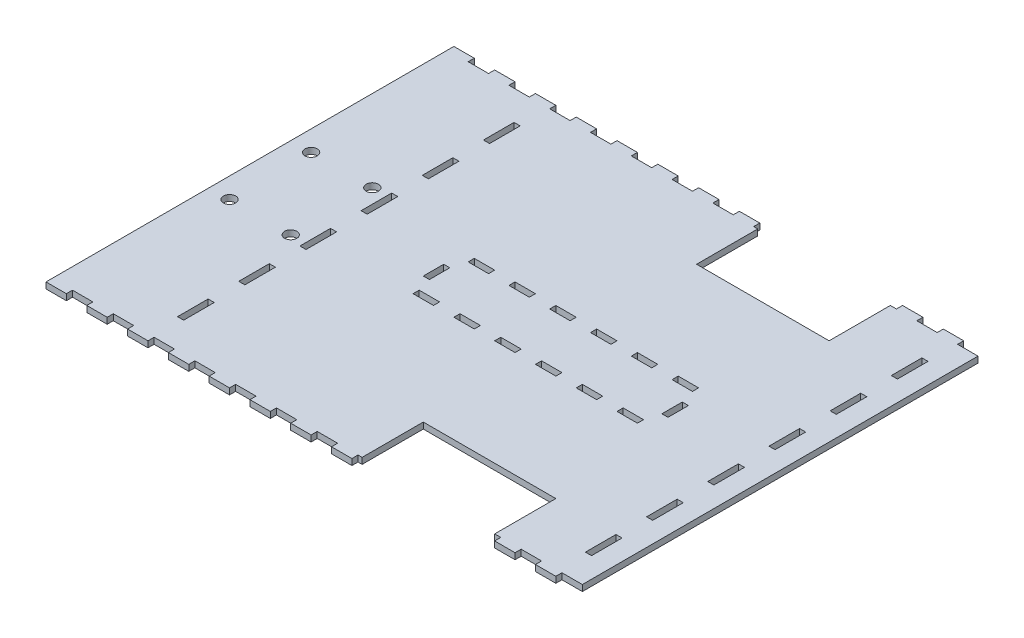
SolidWorks part; units mm, degrees
ref_plane "Front Plane" through (0, 0, 0) normal (0, 0, 1) x (1, 0, 0)
ref_plane "Top Plane" through (0, 0, 0) normal (0, 1, 0) x (1, 0, 0)
ref_plane "Right Plane" through (0, 0, 0) normal (1, 0, 0) x (0, 0, -1)
sketch "Sketch3" plane through (0, 0, 0) normal (0, 1, 0) x (1, 0, 0)
  line L0 (0, 0) -> (-300, 0) construction
  line L1 (-300, -97) -> (-300, 97)
  line L2 (-290, 100) -> (-300, 100)
  line L3 (-290, 97) -> (-290, 100)
  line L4 (-280, 97) -> (-290, 97)
  line L5 (-300, 100) -> (-300, 97)
  line L6 (-270, 100) -> (-280, 100)
  line L7 (-270, 97) -> (-270, 100)
  line L8 (-260, 97) -> (-270, 97)
  line L9 (-280, 100) -> (-280, 97)
  line L10 (-250, 100) -> (-260, 100)
  line L11 (-250, 97) -> (-250, 100)
  line L12 (-240, 97) -> (-250, 97)
  line L13 (-260, 100) -> (-260, 97)
  line L14 (-150, -100) -> (-150, 100) construction
  line L15 (-230, 100) -> (-240, 100)
  line L16 (-230, 97) -> (-230, 100)
  line L17 (-220, 97) -> (-230, 97)
  line L18 (-240, 100) -> (-240, 97)
  line L19 (-210, 100) -> (-220, 100)
  line L20 (-210, 97) -> (-210, 100)
  line L21 (-200, 97) -> (-210, 97)
  line L22 (-40, 97) -> (-40, -97)
  line L23 (-50, 37.5) -> (-53, 37.5)
  line L24 (-50, 7.5) -> (-53, 7.5)
  line L25 (-50, -45.947) -> (-50, 45.947) construction
  line L26 (-250, 37.5) -> (-253, 37.5)
  line L27 (-250, 7.5) -> (-253, 7.5)
  line L28 (-250, 48.5) -> (-250, -48.5) construction
  line L29 (-250, 48.5) -> (-223, 48.5) construction
  line L30 (-223, 48.5) -> (-223, -48.5) construction
  line L31 (-210, 15) -> (-90, 15) construction
  line L32 (-90, 15) -> (-90, 5) construction
  line L33 (-50, 7.5) -> (-50, 22.5)
  line L34 (-220, 100) -> (-220, 97)
  line L35 (-190, 100) -> (-200, 100)
  line L36 (-190, 97) -> (-190, 100)
  line L37 (-180, 97) -> (-190, 97)
  line L38 (-200, 100) -> (-200, 97)
  line L39 (-170, 100) -> (-180, 100)
  line L40 (-170, 97) -> (-170, 100)
  line L41 (-160, 97) -> (-170, 97)
  line L42 (-180, 100) -> (-180, 97)
  line L43 (-150, 100) -> (-160, 100)
  line L44 (-150, 97) -> (-150, 100)
  line L45 (-140, 97) -> (-150, 97)
  line L46 (-160, 100) -> (-160, 97)
  line L47 (-130, 100) -> (-140, 100)
  line L48 (-130, 97) -> (-130, 100)
  line L49 (-120, 97) -> (-130, 97)
  line L50 (-140, 100) -> (-140, 97)
  line L51 (-110, 100) -> (-120, 100)
  line L52 (-110, 97) -> (-110, 100)
  line L53 (-100, 97) -> (-110, 97)
  line L54 (-120, 100) -> (-120, 97)
  line L55 (-90, 100) -> (-100, 100)
  line L56 (-90, 97) -> (-90, 100)
  line L57 (-80, 97) -> (-90, 97)
  line L58 (-100, 100) -> (-100, 97)
  line L59 (-70, 100) -> (-80, 100)
  line L60 (-70, 97) -> (-70, 100)
  line L61 (-60, 97) -> (-70, 97)
  line L62 (-80, 100) -> (-80, 97)
  line L63 (-50, 100) -> (-60, 100)
  line L64 (-50, 97) -> (-50, 100)
  line L65 (-40, 97) -> (-50, 97)
  line L66 (-60, 100) -> (-60, 97)
  line L67 (-50, 22.5) -> (-53, 22.5)
  line L68 (-210, -15) -> (-90, -15) construction
  line L69 (-53, 7.5) -> (-53, 22.5)
  line L70 (-50, 37.5) -> (-50, 52.5)
  line L71 (-50, 52.5) -> (-53, 52.5)
  line L72 (-53, 37.5) -> (-53, 52.5)
  line L73 (-50, 67.5) -> (-53, 67.5)
  line L74 (-50, 67.5) -> (-50, 82.5)
  line L75 (-50, 82.5) -> (-53, 82.5)
  line L76 (-60, -100) -> (-60, -97)
  line L77 (-40, -97) -> (-50, -97)
  line L78 (-50, -97) -> (-50, -100)
  line L79 (-50, -100) -> (-60, -100)
  line L80 (-80, -100) -> (-80, -97)
  line L81 (-60, -97) -> (-70, -97)
  line L82 (-70, -97) -> (-70, -100)
  line L83 (-70, -100) -> (-80, -100)
  line L84 (-100, -100) -> (-100, -97)
  line L85 (-80, -97) -> (-90, -97)
  line L86 (-90, -97) -> (-90, -100)
  line L87 (-90, -100) -> (-100, -100)
  line L88 (-120, -100) -> (-120, -97)
  line L89 (-100, -97) -> (-110, -97)
  line L90 (-110, -97) -> (-110, -100)
  line L91 (-110, -100) -> (-120, -100)
  line L92 (-140, -100) -> (-140, -97)
  line L93 (-120, -97) -> (-130, -97)
  line L94 (-130, -97) -> (-130, -100)
  line L95 (-130, -100) -> (-140, -100)
  line L96 (-160, -100) -> (-160, -97)
  line L97 (-140, -97) -> (-150, -97)
  line L98 (-150, -97) -> (-150, -100)
  line L99 (-150, -100) -> (-160, -100)
  line L100 (-180, -100) -> (-180, -97)
  line L101 (-160, -97) -> (-170, -97)
  line L102 (-170, -97) -> (-170, -100)
  line L103 (-170, -100) -> (-180, -100)
  line L104 (-200, -100) -> (-200, -97)
  line L105 (-180, -97) -> (-190, -97)
  line L106 (-190, -97) -> (-190, -100)
  line L107 (-190, -100) -> (-200, -100)
  line L108 (-250, -48.5) -> (-223, -48.5) construction
  line L109 (-250, 7.5) -> (-250, 22.5)
  line L110 (-220, -100) -> (-220, -97)
  line L111 (-53, 67.5) -> (-53, 82.5)
  line L112 (-53, -67.5) -> (-53, -82.5)
  line L113 (-50, -82.5) -> (-53, -82.5)
  line L114 (-200, -97) -> (-210, -97)
  line L115 (-210, -97) -> (-210, -100)
  line L116 (-210, -100) -> (-220, -100)
  line L117 (-240, -100) -> (-240, -97)
  line L118 (-220, -97) -> (-230, -97)
  line L119 (-230, -97) -> (-230, -100)
  line L120 (-230, -100) -> (-240, -100)
  line L121 (-50, -67.5) -> (-50, -82.5)
  line L122 (-260, -100) -> (-260, -97)
  line L123 (-240, -97) -> (-250, -97)
  line L124 (-250, -97) -> (-250, -100)
  line L125 (-250, -100) -> (-260, -100)
  line L126 (-280, -100) -> (-280, -97)
  line L127 (-260, -97) -> (-270, -97)
  line L128 (-270, -97) -> (-270, -100)
  line L129 (-270, -100) -> (-280, -100)
  line L130 (-300, -100) -> (-300, -97)
  line L131 (-210, 15) -> (-210, -15) construction
  line L132 (-115, 15) -> (-125, 15)
  line L133 (-90, 5) -> (-93, 5)
  line L134 (-90, 5) -> (-90, -5)
  line L135 (-90, -5) -> (-93, -5)
  line L136 (-93, 5) -> (-93, -5)
  line L137 (-95, 15) -> (-105, 15)
  line L138 (-95, 15) -> (-95, 12)
  line L139 (-95, 12) -> (-105, 12)
  line L140 (-105, 15) -> (-105, 12)
  line L141 (-115, 12) -> (-125, 12)
  line L142 (-125, 15) -> (-125, 12)
  line L143 (-135, 15) -> (-145, 15)
  line L144 (-135, 12) -> (-145, 12)
  line L145 (-145, 15) -> (-145, 12)
  line L146 (-155, 15) -> (-165, 15)
  line L147 (-155, 12) -> (-165, 12)
  line L148 (-165, 15) -> (-165, 12)
  line L149 (-175, 15) -> (-185, 15)
  line L150 (-175, 12) -> (-185, 12)
  line L151 (-185, 15) -> (-185, 12)
  line L152 (-195, 15) -> (-205, 15)
  line L153 (-195, 12) -> (-205, 12)
  line L154 (-205, 15) -> (-205, 12)
  line L155 (-195, 12) -> (-195, 15)
  line L156 (-175, 12) -> (-175, 15)
  line L157 (-155, 12) -> (-155, 15)
  line L158 (-135, 12) -> (-135, 15)
  line L159 (-115, 12) -> (-115, 15)
  line L160 (-207, 5) -> (-207, -5)
  line L161 (-210, -5) -> (-207, -5)
  line L162 (-210, 5) -> (-210, -5)
  line L163 (-210, 5) -> (-207, 5)
  line L164 (-115, -12) -> (-115, -15)
  line L165 (-135, -12) -> (-135, -15)
  line L166 (-155, -12) -> (-155, -15)
  line L167 (-175, -12) -> (-175, -15)
  line L168 (-195, -12) -> (-195, -15)
  line L169 (-205, -15) -> (-205, -12)
  line L170 (-195, -12) -> (-205, -12)
  line L171 (-195, -15) -> (-205, -15)
  line L172 (-185, -15) -> (-185, -12)
  line L173 (-175, -12) -> (-185, -12)
  line L174 (-175, -15) -> (-185, -15)
  line L175 (-165, -15) -> (-165, -12)
  line L176 (-155, -12) -> (-165, -12)
  line L177 (-155, -15) -> (-165, -15)
  line L178 (-145, -15) -> (-145, -12)
  line L179 (-135, -12) -> (-145, -12)
  line L180 (-135, -15) -> (-145, -15)
  line L181 (-125, -15) -> (-125, -12)
  line L182 (-115, -12) -> (-125, -12)
  line L183 (-105, -15) -> (-105, -12)
  line L184 (-95, -12) -> (-105, -12)
  line L185 (-95, -15) -> (-95, -12)
  line L186 (-95, -15) -> (-105, -15)
  line L187 (-115, -15) -> (-125, -15)
  line L188 (-250, 22.5) -> (-253, 22.5)
  line L189 (-253, 7.5) -> (-253, 22.5)
  line L190 (-250, 37.5) -> (-250, 52.5)
  line L191 (-250, 52.5) -> (-253, 52.5)
  line L192 (-253, 37.5) -> (-253, 52.5)
  line L193 (-250, 67.5) -> (-253, 67.5)
  line L194 (-250, 67.5) -> (-250, 82.5)
  line L195 (-250, 82.5) -> (-253, 82.5)
  line L196 (-253, 67.5) -> (-253, 82.5)
  line L197 (-253, -67.5) -> (-253, -82.5)
  line L198 (-250, -82.5) -> (-253, -82.5)
  line L199 (-250, -67.5) -> (-250, -82.5)
  line L200 (-250, -67.5) -> (-253, -67.5)
  line L201 (-253, -37.5) -> (-253, -52.5)
  line L202 (-250, -52.5) -> (-253, -52.5)
  line L203 (-250, -37.5) -> (-250, -52.5)
  line L204 (-253, -7.5) -> (-253, -22.5)
  line L205 (-250, -22.5) -> (-253, -22.5)
  line L206 (-250, -7.5) -> (-250, -22.5)
  line L207 (-250, -7.5) -> (-253, -7.5)
  line L208 (-250, -37.5) -> (-253, -37.5)
  line L209 (-50, -67.5) -> (-53, -67.5)
  line L210 (-53, -37.5) -> (-53, -52.5)
  line L211 (-50, -52.5) -> (-53, -52.5)
  line L212 (-50, -37.5) -> (-50, -52.5)
  line L213 (-53, -7.5) -> (-53, -22.5)
  line L214 (-50, -22.5) -> (-53, -22.5)
  line L215 (-50, -7.5) -> (-50, -22.5)
  line L216 (-50, -7.5) -> (-53, -7.5)
  line L217 (-50, -37.5) -> (-53, -37.5)
  line L231 (-280, -97) -> (-290, -97)
  line L232 (-290, -97) -> (-290, -100)
  line L233 (-290, -100) -> (-300, -100)
  circle A0 centre (-290, 20) radius 3
  circle A1 centre (-260, 20) radius 3
  circle A2 centre (-260, -20) radius 3
  circle A3 centre (-290, -20) radius 3
  point P31 (-250, 36)
  point P80 (-91.5, 0)
  point P82 (-150, 0)
  point P126 (-223, 0)
  point P128 (-250, 18)
  point P129 (-50, 0)
  point P150 (-150, -15)
  point P151 (-150, 15)
  point P183 (-208.5, 0)
  point P212 (-223, 18)
  point P218 (-223, 36)
  dimension "D17" = 6
  dimension "D18" = 6
  dimension "D1" = 300
  dimension "D4" = 7.5
  dimension "D5" = 100
  dimension "D6" = 97
  dimension "D7" = 15
  dimension "D8" = 97
  dimension "D9" = 3
  dimension "D10" = 3
  dimension "D11" = 48.5
  dimension "D12" = 27
  dimension "D13" = 60
  dimension "D14" = 15
  dimension "D15" = 30
  dimension "D16" = 20
  dimension "D19" = 194
  dimension "D20" = 10
  dimension "D21" = 3
  dimension "D22" = 7.5
  dimension "D23" = 15
  dimension "D24" = 3
  dimension "D25" = 3
  dimension "D29" = 10
  dimension "D30" = 3
  dimension "D31" = 10
  dimension "D32" = 3
  dimension "D33" = 10
  dimension "D34" = 5
  dimension "D35" = 6
  dimension "D36" = 3
extrude "Boss-Extrude1" add sketch "Sketch3" along normal blind 3 contours L1 L116 L115 L107 L106 L83 L82 L79 L95 L98 L99 L91 L90 L86 region at (-170.2077, 0, 0)
sketch "Sketch4" plane through (0, 3, 0) normal (0, 1, 0) x (1, 0, 0)
  line L0 (-80, 97) -> (-90, 97) construction
  line L1 (-83, 97) -> (-148, 97)
  line L2 (-83, 97) -> (-83, 67)
  line L3 (-83, 67) -> (-148, 67)
  line L4 (-148, 97) -> (-148, 67)
  line L5 (-53, 67.5) -> (-53, 82.5) construction
  line L6 (-40, 0) -> (-300, 0) construction
  line L7 (-40, 97) -> (-40, -97) construction
  line L8 (-300, 100) -> (-300, -100) construction
  line L9 (-148, -97) -> (-148, -67)
  line L10 (-83, -67) -> (-148, -67)
  line L11 (-83, -97) -> (-83, -67)
  line L12 (-83, -97) -> (-148, -97)
  dimension "D1" = 65
  dimension "D2" = 30
  dimension "D3" = 30
extrude "Cut-Extrude1" cut sketch "Sketch4" against normal blind 10
